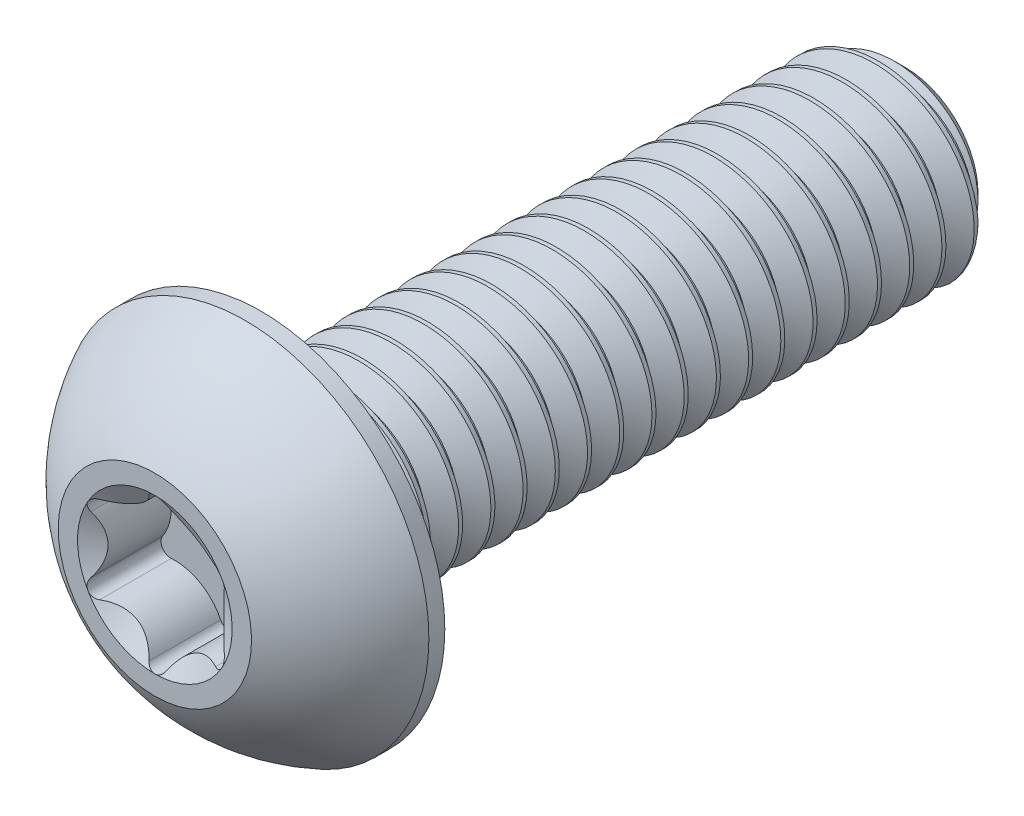
SolidWorks part; units mm, degrees
material "Alloy Steel"
ref_plane "Front" through (0, 0, 0) normal (0, 0, 1) x (1, 0, 0)
ref_plane "Top" through (0, 0, 0) normal (0, 1, 0) x (1, 0, 0)
ref_plane "Right" through (0, 0, 0) normal (1, 0, 0) x (0, 0, -1)
sketch "Sketch1" plane through (0, 0, 0) normal (1, 0, 0) x (0, 0, -1)
  line L2 (1.65, 1.5) -> (11.65, 1.5)
  line L3 (11.65, 1.5) -> (11.65, 0)
  line L4 (11.65, 0) -> (1.65, 0)
  line L6 (1.4025, 2.85) -> (1.65, 2.85) construction
  line L7 (11.65, 1.5) -> (11.65, -1.5) construction
  line L8 (0, 0) -> (1.65, 0) construction
  line L9 (1.65, 2.85) -> (1.65, -2.85) construction
  line L11 (1.65, 1.5) -> (1.65, 0)
  line L14 (0, 0) -> (0, 1.5) construction
  arc A3 (0, 1.5) -> (1.4025, 2.85) centre (2.7948, 0) cw construction
  dimension "D1" = 0.2475
revolve "Revolve1" add sketch "Sketch1" angle 360 mid plane about L4
sketch "Sketch3" plane through (0, 0, -11.65) normal (0, 0, -1) x (-1, 0, 0)
  circle A0 centre (0, 0) radius 1.5
curve "Helix/Spiral1" pitch 0.5 height 10.5 radius 1.5 centre (0, 0, -11.65) axis (0, 0, 1) start towards (0, 1, 0)
sketch "Sketch2" plane through (0, 0, 0) normal (1, 0, 0) x (0, 0, -1)
  line L0 (11.65, 1.5) -> (12.0875, 1.5)
  line L1 (12.0875, 1.5) -> (11.9, 1.1752)
  line L2 (11.9, 1.1752) -> (11.8375, 1.1752)
  line L3 (11.8375, 1.1752) -> (11.65, 1.5)
  line L4 (11.7438, 1.3376) -> (11.9938, 1.3376) construction
  dimension "D1" = 60
  dimension "D2" = 0.0625
  dimension "D3" = 0.25
chamfer "Chamfer1" distance 0.375 angle 45 1 edges at (0, 1.5, -11.65)
sweep "Cut-Sweep1" cut profiles "Sketch2" path "Helix/Spiral1" align with end faces yes
sketch "Sketch7" plane through (0, 0, 0) normal (1, 0, 0) x (0, 0, -1)
  line L0 (0, 0) -> (0, 1.5) construction
  line L6 (1.4025, 2.85) -> (1.65, 2.85) construction
  line L8 (0, 0) -> (1.65, 0) construction
  line L11 (1.65, 2.85) -> (1.65, -2.85) construction
  line L12 (1.4025, 2.85) -> (1.65, 2.85)
  line L13 (0, 0) -> (1.65, 0)
  line L15 (1.65, 2.85) -> (1.65, 0)
  line L16 (0, 1.5) -> (0, 0)
  arc A2 (1.4025, 2.85) -> (0, 1.5) centre (2.7948, 0) ccw construction
  arc A3 (1.4025, 2.85) -> (0, 1.5) centre (2.7948, 0) ccw
revolve "Revolve2" add sketch "Sketch7" angle 360 mid plane about L13
sketch "Sketch11" plane through (0, 0, 0) normal (0, 0, 1) x (1, 0, 0)
  line L0 (0, 0) -> (-1.0392, 0.6)
  line L1 (0, 0) -> (-1.0392, -0.6)
  line L2 (0, 1.2) -> (0, 1.05) construction
  line L3 (0, 1.05) -> (0, 0.9) construction
  line L4 (3.135, 0) -> (-3.135, 0) construction
  circle A0 centre (0, 0) radius 0.9 construction
  circle A1 centre (0, 0) radius 1.05 construction
  circle A2 centre (0, 0) radius 1.2 construction
  arc A3 (-1.034, 0.4416) -> (-1.034, -0.4416) centre (-1.6946, 0) cw
  arc A4 (-1.034, 0.4416) -> (-1.0392, 0.6) centre (-0.9093, 0.525) cw
  arc A5 (-1.034, -0.4416) -> (-1.0392, -0.6) centre (-0.9093, -0.525) ccw
  dimension "D1" = 1.8
  dimension "D2" = 2.4
  dimension "D3" = 30
extrude "Cut-Extrude4" cut sketch "Sketch11" against normal blind 1.155
pattern_circular "CirPattern1" count 6 over 360 of "Cut-Extrude4"
sketch "Sketch6" plane through (0, 0, 0) normal (0, 0, 1) x (1, 0, 0)
  circle A0 centre (0, 0) radius 1.2 construction
  circle A1 centre (0, 0) radius 1.2
extrude "Cut-Extrude3" cut sketch "Sketch6" against normal blind 1.155 draft 60
sketch "Sketch9" [suppressed] plane through (0, 0, -5.5) normal (0, 0, 1) x (1, 0, 0)
  circle A2 centre (0, 0) radius 5
extrude "Boss-Extrude2" [suppressed] add sketch "Sketch9" against normal offset from surface (13 mm away) 32 up to face at (0, 1.125, -11.65)
sketch "Sketch10" plane through (0, 0, 0) normal (1, 0, 0) x (0, 0, -1)
  line L0 (11.65, 1.5) -> (11.65, -1.5) construction
  point P0 (10.9, -1.5)
  dimension "D1" = 0.75
equation "\"D3@Helix/Spiral1\" = \"Lg@Sketch1\" + \"D4@Helix/Spiral1\""
equation "\"D2@Sketch2\" = \"D4@Helix/Spiral1\" * .125"
equation "\"D3@Sketch2\" = \"D4@Helix/Spiral1\" * .5"
equation "\"D1@Chamfer1\" = \"D4@Helix/Spiral1\" * .75"
equation "\"D1@Sketch1\" = \"Head Ht@Sketch1\" * .15"
equation "\"D1@Sketch10\" = \"D4@Helix/Spiral1\" * 1.5"
equation "\"D2@Sketch11\" = \"Dia@Sketch1\" * .8"
equation "\"D1@Sketch11\" = \"D2@Sketch11\" * .75"
equation "\"D1@Cut-Extrude4\" = \"Head Ht@Sketch1\" * .7"
equation "\"D1@Cut-Extrude3\" = \"D1@Cut-Extrude4\""
